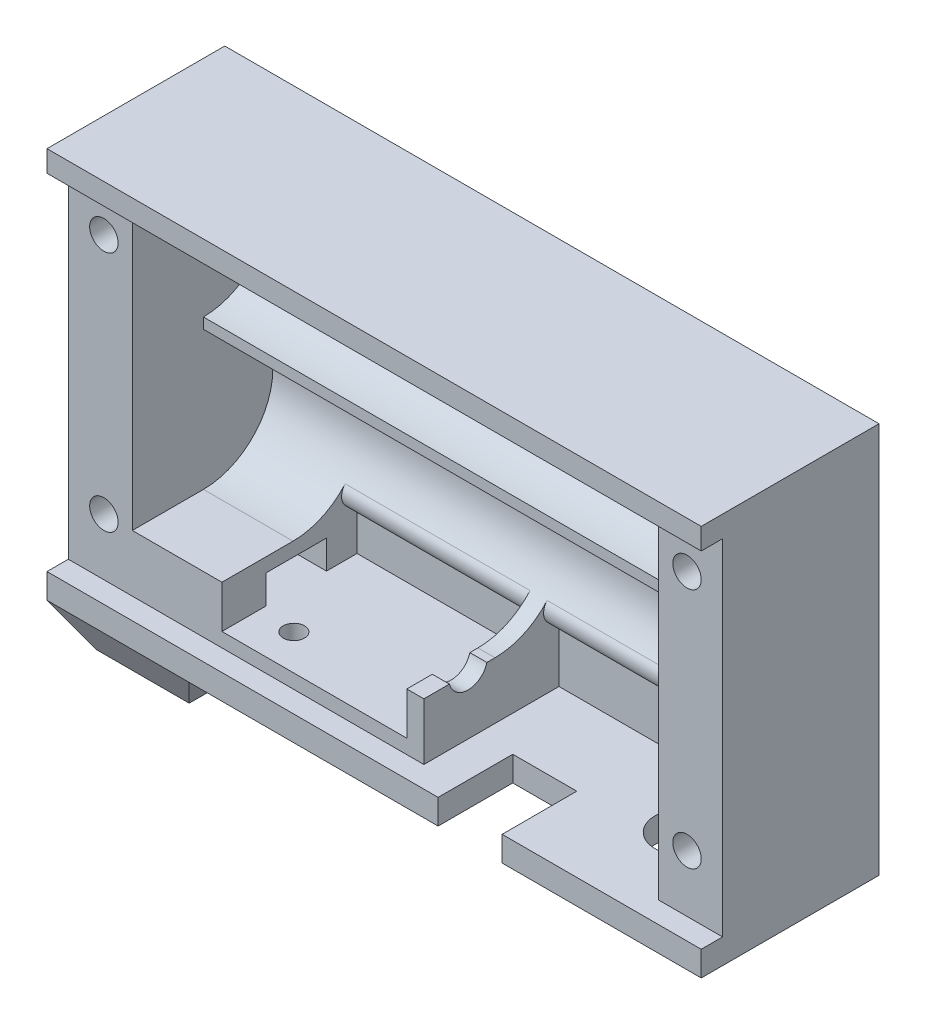
SolidWorks part; units mm, degrees
material "ABS"
ref_plane "Front Plane" through (0, 0, 0) normal (0, 0, 1) x (1, 0, 0)
ref_plane "Top Plane" through (0, 0, 0) normal (0, 1, 0) x (1, 0, 0)
ref_plane "Right Plane" through (0, 0, 0) normal (1, 0, 0) x (0, 0, -1)
sketch "Sketch1" plane through (0, 0, 0) normal (0, 0, 1) x (1, 0, 0)
  line L1 (-46, 27.5) -> (46, 27.5)
  line L2 (-46, 27.5) -> (-46, -27.5)
  line L3 (-46, -27.5) -> (46, -27.5)
  line L4 (46, 27.5) -> (46, -27.5)
  line L5 (-46, 27.5) -> (46, -27.5) construction
  line L6 (-46, -27.5) -> (46, 27.5) construction
  point P0 (0, 0)
  dimension "D1" = 92
  dimension "D2" = 55
extrude "Body" add sketch "Sketch1" along normal blind 25
sketch "Sketch2" plane through (0, 0, 0) normal (1, 0, 0) x (0, 0, -1)
  line L0 (-12, 5) -> (-12, 3.5)
  line L1 (-12, 24.5) -> (-28.2216, 24.5)
  line L2 (-28.2216, 24.5) -> (-28.2216, -16)
  line L3 (-12, -16) -> (-28.2216, -16)
  line L4 (-25, 27.5) -> (0, 27.5) construction
  line L5 (0, -27.5) -> (0, 27.5) construction
  circle A0 centre (-12, 14.75) radius 9.75
  circle A1 centre (-12, -6.25) radius 9.75
  dimension "D1" = 19.5
  dimension "D2" = 21
  dimension "D3" = 3
  dimension "D4" = 12
extrude "Battery" cut sketch "Sketch2" against normal mid plane 74 contours A1 L0 A0 L1 L2 L3 | A1 | A0 region at (0, 4.25, 23.4219) region at (0, 14.75, 12) region at (0, -6.25, 12)
sketch "Sketch3" plane through (0, 0, 25) normal (0, 0, 1) x (1, 0, 0)
  line L1 (37, -16) -> (4, -16)
  line L2 (37, -16) -> (37, -24)
  line L3 (37, -24) -> (4, -24)
  line L4 (4, -16) -> (4, -24)
  dimension "D1" = 33
  dimension "D2" = 8
extrude "Controller" cut sketch "Sketch3" against normal blind 22
sketch "Sketch4" plane through (0, -27.5, 0) normal (0, -1, 0) x (1, 0, 0)
  line L0 (46, 25) -> (46, 0) construction
  line L1 (-46, 25) -> (46, 25) construction
  circle A0 centre (30.5, 12) radius 4
  dimension "D1" = 8
  dimension "D2" = 15.5
  dimension "D3" = 13
extrude "Cut-Extrude3" cut sketch "Sketch4" against normal up to next
sketch "Sketch5" plane through (0, -27.5, 0) normal (0, -1, 0) x (1, 0, 0)
  line L0 (-46, 25) -> (46, 25) construction
  line L1 (9, 25) -> (18, 25)
  line L2 (9, 25) -> (9, 14.5)
  line L3 (9, 14.5) -> (18, 14.5)
  line L4 (18, 25) -> (18, 14.5)
  dimension "D1" = 9
  dimension "D2" = 10.5
  dimension "D3" = 12.5
extrude "Connector" cut sketch "Sketch5" against normal up to next
sketch "Sketch6" plane through (0, 0, 25) normal (0, 0, 1) x (1, 0, 0)
  line L0 (4, -16) -> (-37, -16) construction
  line L1 (1.6, -16) -> (-24.4, -16)
  line L2 (1.6, -16) -> (1.6, -22)
  line L3 (1.6, -22) -> (-24.4, -22)
  line L4 (-24.4, -16) -> (-24.4, -22)
  line L5 (4, -16) -> (4, -24) construction
  dimension "D1" = 26
  dimension "D2" = 6
  dimension "D3" = 2.4
extrude "Charger" cut sketch "Sketch6" against normal blind 22
sketch "Sketch7" plane through (0, -27.5, 0) normal (0, -1, 0) x (-1, 0, 0)
  line L0 (46, -25) -> (-9, -25) construction
  circle A0 centre (19.2864, -17) radius 1.5
  dimension "D1" = 3
  dimension "D2" = 8
extrude "ChgLED" cut sketch "Sketch7" against normal up to next
sketch "Sketch8" plane through (0, -27.5, 0) normal (0, -1, 0) x (1, 0, 0)
  line L0 (-46, 0) -> (46, 0) construction
  line L1 (-46, 25) -> (-26, 25)
  line L2 (-46, 25) -> (-46, 0)
  line L3 (-46, 0) -> (-26, 0)
  line L4 (-26, 25) -> (-26, 0)
  dimension "D1" = 20
extrude "Boss-Extrude1" add sketch "Sketch8" along normal blind 6 draft 30
sketch "Sketch9" plane through (0, -33.5, 0) normal (0, -1, 0) x (1, 0, 0)
  line L0 (-42.5359, 21.5359) -> (-42.5359, 3.4641) construction
  line L1 (-31, 19.5) -> (-41, 19.5)
  line L2 (-31, 19.5) -> (-31, 5.5)
  line L3 (-31, 5.5) -> (-41, 5.5)
  line L4 (-41, 19.5) -> (-41, 5.5)
  line L5 (-29.4641, 3.4641) -> (-29.4641, 21.5359) construction
  line L6 (-29.4641, 21.5359) -> (-42.5359, 21.5359) construction
  point P4 (-41, 12.5)
  point P7 (-42.5359, 12.5)
  point P10 (-29.4641, 12.5)
  point P13 (-36, 21.5359)
  point P14 (-36, 19.5)
  point P15 (-36, 5.5)
  dimension "D1" = 10
  dimension "D2" = 14
extrude "Cut-Extrude7" cut sketch "Sketch9" against normal blind 15
sketch "Sketch10" plane through (-24.4, 0, 0) normal (1, 0, 0) x (0, 0, -1)
  line L0 (-3, -22) -> (-25, -22) construction
  line L1 (-7.2966, -22) -> (-15.8121, -22)
  line L2 (-7.2966, -22) -> (-7.2966, -17.9695)
  line L3 (-7.2966, -17.9695) -> (-15.8121, -17.9695)
  line L4 (-15.8121, -22) -> (-15.8121, -17.9695)
extrude "Cut-Extrude8" cut sketch "Sketch10" against normal blind 15
sketch "Sketch11" plane through (46, 0, 0) normal (1, 0, 0) x (0, 0, -1)
  line L0 (-25, -27.5) -> (-25, 27.5) construction
  line L1 (-25, 24.5) -> (-22, 24.5)
  line L2 (-25, 24.5) -> (-25, -24)
  line L3 (-25, -24) -> (-22, -24)
  line L4 (-22, 24.5) -> (-22, -24)
  dimension "D1" = 3
extrude "Cut-Extrude9" cut sketch "Sketch11" against normal through all
hole_wizard "Ø4.0mm Dowel Hole1" positions "Sketch12" profile "Sketch13" hole size "Ø4.0" standard "ANSI Metric"
sketch "Sketch12" plane through (0, 0, 22) normal (0, 0, 1) x (1, 0, 0)
  point P0 (41, 18)
  dimension "D1" = 41
  dimension "D2" = 18
sketch "Sketch13" plane through (41, 18, 22) normal (1, 0, 0) x (0, -1, 0)
  line L0 (0, 0) -> (0, 16.2017)
  line L1 (0, 16.2017) -> (2, 15)
  line L2 (2, 15) -> (2, 0)
  line L5 (2, 0) -> (0, 0)
  line L10 (0, 16.2017) -> (-2, 15) construction
  line L11 (0, -6.35) -> (0, 107.95) construction
  dimension "Hole Dia." = 4
  dimension "Hole Depth" = 15
  dimension "Drill Angle" = 118
pattern_linear "LPattern1" count 2 spacing 82 along (-1, 0, 0) count 2 spacing 34 along (0, -1, 0) of "Ø4.0mm Dowel Hole1"
fillet "Fillet1" radius 2 2 edges at (-11.4, -16, 12) (20.5, -16, 12)
sketch "Sketch14" plane through (0, 0, 0) normal (1, 0, 0) x (0, 0, -1)
  circle A0 centre (-15.7772, -15.2983) radius 2.7301
  point P2 (-15.7772, -15.2983)
  point P3 (0, 0)
extrude "Cut-Extrude10" cut sketch "Sketch14" along normal blind 10
